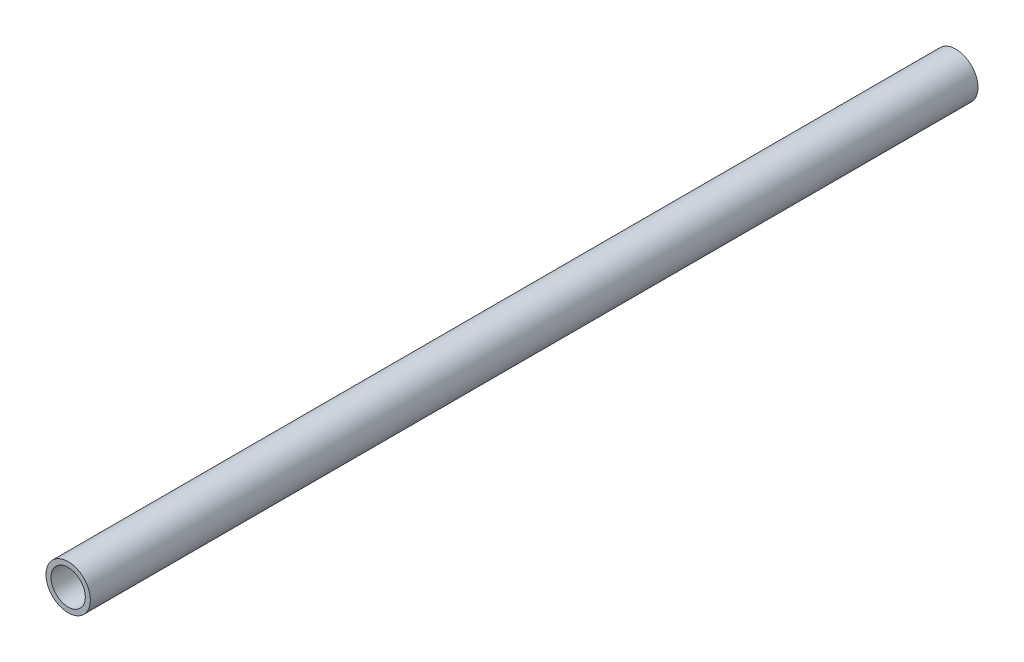
SolidWorks part; units mm, degrees
material "Hexcel AS4C (3000 Filaments)"
ref_plane "Front Plane" through (0, 0, 0) normal (0, 0, 1) x (1, 0, 0)
ref_plane "Top Plane" through (0, 0, 0) normal (0, 1, 0) x (1, 0, 0)
ref_plane "Right Plane" through (0, 0, 0) normal (1, 0, 0) x (0, 0, -1)
sketch "Sketch2" plane through (0, 0, 0) normal (0, 0, 1) x (1, 0, 0)
  circle A0 centre (0, 0) radius 4.7625
  circle A1 centre (0, 0) radius 3.683
  dimension "D1" = 9.525
  dimension "D2" = 7.366
extrude "Boss-Extrude1" add sketch "Sketch2" along normal mid plane 190.5
